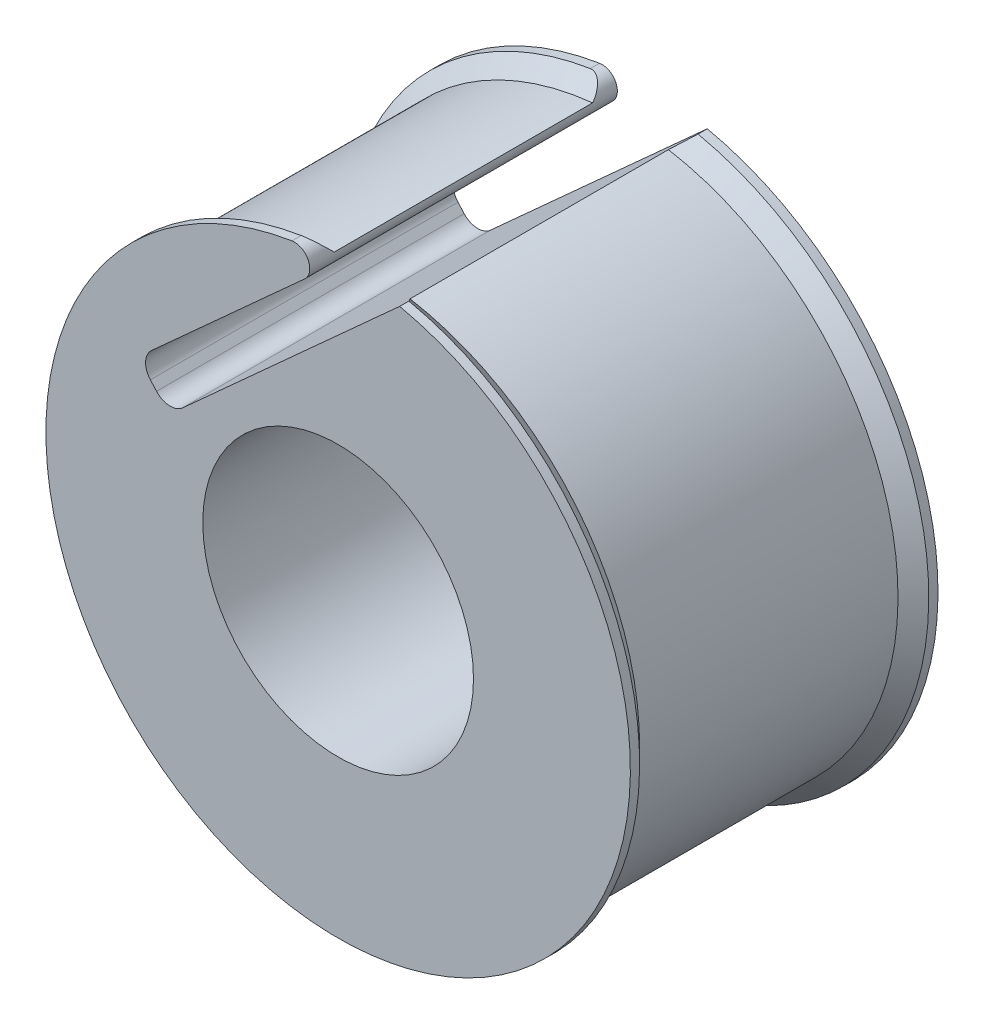
SolidWorks part; units mm, degrees
ref_plane "Front Plane" through (0, 0, 0) normal (0, 0, 1) x (1, 0, 0)
ref_plane "Top Plane" through (0, 0, 0) normal (0, 1, 0) x (1, 0, 0)
ref_plane "Right Plane" through (0, 0, 0) normal (1, 0, 0) x (0, 0, -1)
sketch "Sketch1" plane through (0, 0, 0) normal (0, 0, 1) x (1, 0, 0)
  circle A0 centre (0, 0) radius 4.4
  circle A1 centre (0, 0) radius 9.5
  dimension "D1" = 8.8
  dimension "D2" = 19
extrude "Boss-Extrude1" add sketch "Sketch1" along normal mid plane 10
sketch "Sketch2" plane through (0, 0, 5) normal (0, 0, 1) x (1, 0, 0)
  line L0 (0, 9.5) -> (-6.5065, 3.6122)
  line L1 (-6.5065, 3.6122) -> (-5.5, 2.5)
  line L2 (-5.5, 2.5) -> (2.0002, 9.287)
  circle A0 centre (0, 0) radius 9.5 construction
  arc A2 (2.0002, 9.287) -> (0, 9.5) centre (0, 0) ccw
  dimension "D1" = 1.5
  dimension "D2" = 2.5
  dimension "D3" = 5.5
extrude "Cut-Extrude1" cut sketch "Sketch2" against normal through all
sketch "Sketch3" plane through (0, 0, 0) normal (0, 0, 1) x (1, 0, 0)
  circle A0 centre (0, 0) radius 9
  circle A1 centre (0, 0) radius 9.5
  arc A2 (0, 9.5) -> (2.0002, 9.287) centre (0, 0) ccw construction
  dimension "D1" = 18
extrude "Cut-Extrude2" cut sketch "Sketch3" against normal mid plane 8
chamfer "Chamfer1" distance 0.7 angle 45 2 edges at (-1.0058, -9.4466, 4) (-1.0058, -9.4466, -4)
fillet "Fillet1" radius 0.5 2 edges at (0, 9.5, 4.85) (0, 9.5, -4.85)
fillet "Fillet2" radius 0.6 2 edges at (-6.5065, 3.6122, 0) (-5.5, 2.5, 0)
